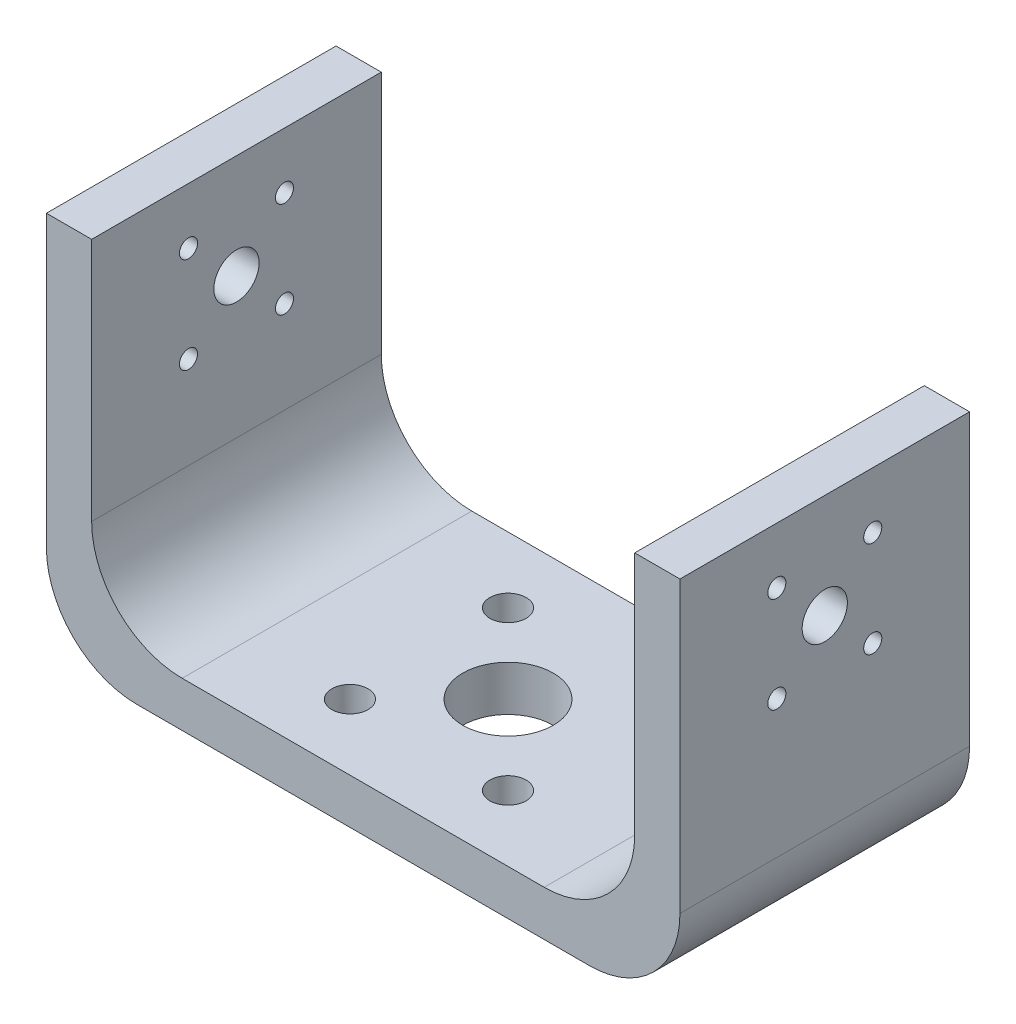
SolidWorks part; units mm, degrees
ref_plane "Front Plane" through (0, 0, 0) normal (0, 0, 1) x (1, 0, 0)
ref_plane "Top Plane" through (0, 0, 0) normal (0, 1, 0) x (1, 0, 0)
ref_plane "Right Plane" through (0, 0, 0) normal (1, 0, 0) x (0, 0, -1)
sketch "Sketch1" plane through (0, 0, 0) normal (0, 1, 0) x (1, 0, 0)
  line L1 (-35, 0) -> (35, 0)
  line L2 (-35, 0) -> (-35, -32)
  line L3 (-35, -32) -> (35, -32)
  line L4 (35, 0) -> (35, -32)
  dimension "D1" = 70
  dimension "D2" = 32
extrude "Boss-Extrude1" add sketch "Sketch1" along normal blind 5
sketch "Sketch2" plane through (0, 5, 0) normal (0, 1, 0) x (1, 0, 0)
  line L0 (-35, 0) -> (-35, -32) construction
  line L1 (-35, 0) -> (-30, 0)
  line L2 (-35, 0) -> (-35, -32)
  line L3 (-35, -32) -> (-30, -32)
  line L5 (0, 0) -> (0, -32) construction
  line L6 (35, 0) -> (-35, 0) construction
  line L7 (-35, -32) -> (35, -32) construction
  line L8 (35, -32) -> (30, -32)
  line L10 (35, 0) -> (30, 0)
  line L11 (35, 0) -> (35, -32)
  line L12 (-30, 0) -> (-30, -32)
  line L13 (30, 0) -> (30, -32)
  circle A0 centre (-8.7328, -24.7328) radius 1.5 construction
  circle A1 centre (8.7328, -24.7328) radius 1.5 construction
  circle A2 centre (8.7328, -7.2672) radius 1.5 construction
  circle A3 centre (-8.7328, -7.2672) radius 1.5 construction
  circle A4 centre (-8.7328, -24.7328) radius 1.5 construction
  circle A5 centre (8.7328, -24.7328) radius 1.5 construction
  circle A6 centre (8.7328, -7.2672) radius 1.5 construction
  circle A7 centre (-8.7328, -7.2672) radius 1.5 construction
  point P1 (15.986, 0)
  point P12 (-35, -16)
  point P13 (0, -16)
  point P15 (15.986, -32)
  dimension "D2" = 5
  dimension "D1" = 5
extrude "Boss-Extrude2" add sketch "Sketch2" along normal blind 37
sketch "Sketch3" plane through (0, 0, 0) normal (0, -1, 0) x (1, 0, 0)
  line L4 (-35, 32) -> (-35, 0)
  line L5 (-35, 0) -> (35, 0)
  line L6 (35, 0) -> (35, 32)
  line L7 (35, 32) -> (-35, 32)
  line L8 (-35, 32) -> (-35, 0) construction
  line L9 (-35, 0) -> (35, 0) construction
  line L10 (35, 0) -> (35, 32) construction
  line L11 (35, 32) -> (-35, 32) construction
  circle A0 centre (0, 16) radius 5
  circle A9 centre (-8.7328, 7.2672) radius 2
  circle A10 centre (-8.7328, 24.7328) radius 2
  circle A11 centre (8.7328, 24.7328) radius 2
  circle A12 centre (8.7328, 7.2672) radius 2
  point P10 (-35, 16)
  point P12 (0, 32)
  dimension "D1" = 0
  dimension "D2" = 10
extrude "Cut-Extrude1" cut sketch "Sketch3" against normal blind 10
sketch "Sketch4" plane through (-35, 0, 0) normal (-1, 0, 0) x (0, 0, 1)
  line L0 (0, 30.5) -> (32, 30.5) construction
  line L2 (0, 42) -> (32, 42) construction
  line L3 (32, 42) -> (32, 0) construction
  line L4 (0, 42) -> (0, 0) construction
  circle A0 centre (16, 30.5) radius 2.5
  dimension "D2" = 5
  dimension "D1" = 11.5
extrude "Cut-Extrude2" cut sketch "Sketch4" against normal through all
fillet "Fillet1" radius 10 4 edges at (-35, 0, 16) (-30, 5, 16) (30, 5, 16) (35, 0, 16)
sketch "Sketch6" plane through (-35, 0, 0) normal (-1, 0, 0) x (0, 0, 1)
  line L4 (0, 42) -> (0, 10)
  line L5 (0, 10) -> (32, 10)
  line L6 (32, 10) -> (32, 42)
  line L7 (32, 42) -> (0, 42)
  line L11 (32, 42) -> (0, 42) construction
  circle A0 centre (21.3, 25.2) radius 1
  circle A1 centre (16, 30.5) radius 2.5 construction
  circle A2 centre (16, 30.5) radius 2.5 construction
  circle A3 centre (10.7, 25.2) radius 1
  circle A4 centre (10.7, 35.8) radius 1
  circle A5 centre (21.3, 35.8) radius 1
  point P18 (16, 30.5)
  dimension "D2" = 16.8
  dimension "D4" = 2
  dimension "D3" = 10.7
  dimension "D1" = 0
  dimension "D5" = 4
extrude "Cut-Extrude3" cut sketch "Sketch6" against normal through all
